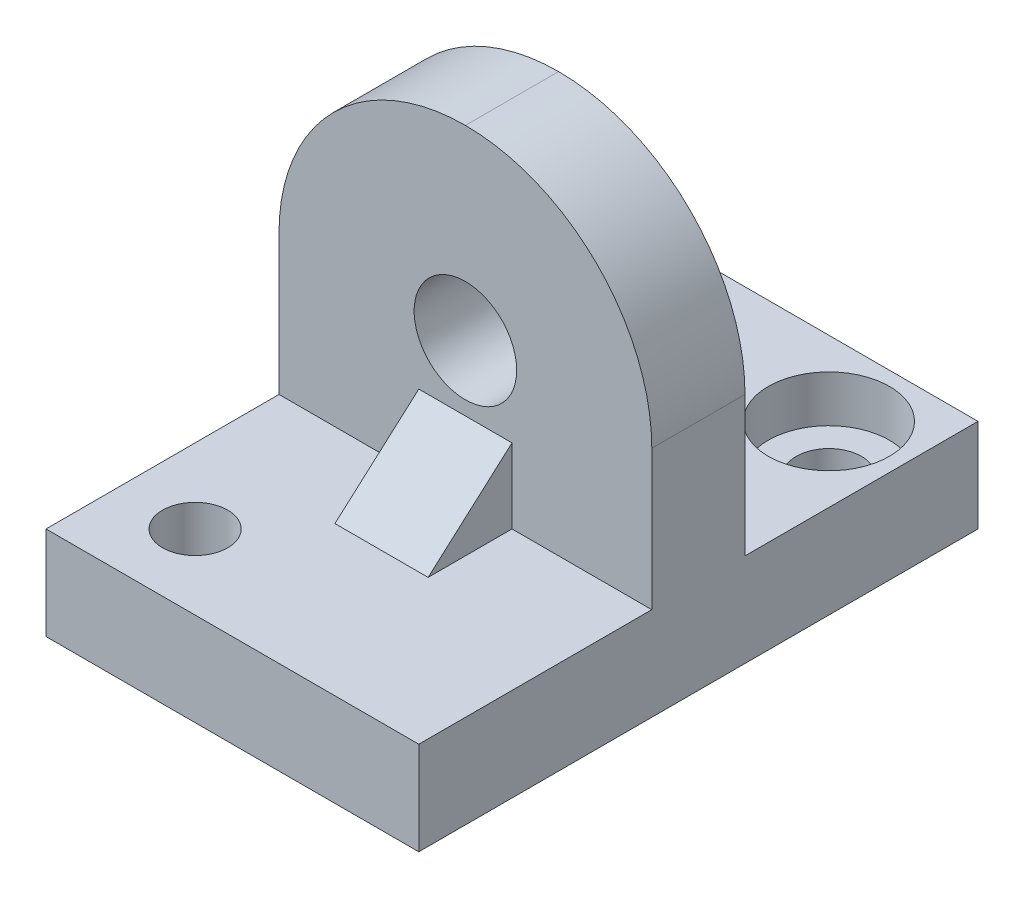
SolidWorks part; units mm, degrees
ref_plane "Спереди" through (0, 0, 0) normal (0, 0, 1) x (1, 0, 0)
ref_plane "Сверху" through (0, 0, 0) normal (0, 1, 0) x (1, 0, 0)
ref_plane "Справа" through (0, 0, 0) normal (1, 0, 0) x (0, 0, -1)
sketch "Эскиз1" plane through (0, 0, 0) normal (1, 0, 0) x (0, 0, -1)
  line L0 (-14, -17.5) -> (-5, -9.5)
  line L1 (-5, -17.5) -> (5, -17.5)
  line L2 (-5, -17.5) -> (-5, 17.5)
  line L3 (-5, 17.5) -> (5, 17.5)
  line L4 (5, -17.5) -> (5, 17.5)
  line L5 (-5, -17.5) -> (5, 17.5) construction
  line L6 (-5, 17.5) -> (5, -17.5) construction
  line L7 (-30, -27.5) -> (30, -27.5)
  line L8 (-30, -27.5) -> (-30, -17.5)
  line L9 (-30, -17.5) -> (30, -17.5)
  line L10 (30, -27.5) -> (30, -17.5)
  line L11 (-30, -27.5) -> (30, -17.5) construction
  line L12 (-30, -17.5) -> (30, -27.5) construction
  line L13 (5, -9.5) -> (14, -17.5)
  point P0 (0, 0)
  point P6 (0, -22.5)
  dimension "D1" = 60
  dimension "D2" = 10
  dimension "D3" = 45
  dimension "D4" = 9
  dimension "D5" = 9
  dimension "D6" = 8
extrude "Бобышка-Вытянуть1" add sketch "Эскиз1" along normal blind 20 and the other way blind 20 contours L1 L4 L3 L2 | L7 L10 L9 L1 L8 region at (0, -22.5, 0) region at (0, 0, 0)
fillet "Скругление1" radius 20 2 edges at (-20, 17.5, 0) (20, 17.5, 0)
sketch "Эскиз2" plane through (0, 0, 5) normal (0, 0, 1) x (1, 0, 0)
  circle A0 centre (0, -2.5) radius 5.5
  dimension "D1" = 11
extrude "Вырез-Вытянуть1" cut sketch "Эскиз2" against normal through all
extrude "Бобышка-Вытянуть2" add sketch "Эскиз1<3>" along normal blind 5 and the other way blind 5 contours L0 L9 L2 | L13 L4 L9 region at (0, -14.8333, 8) region at (0, -14.8333, -8)
sketch "Эскиз1<3>" plane through (0, 0, 0) normal (1, 0, 0) x (0, 0, -1) same geometry as "Эскиз1"
sketch "Эскиз3" plane through (0, -17.5, 0) normal (0, 1, 0) x (1, 0, 0)
  line L0 (-20, -30) -> (20, -30) construction
  line L1 (-20, -30) -> (-20, -5) construction
  line L2 (20, 5) -> (20, 30) construction
  line L3 (-20, 30) -> (20, 30) construction
  circle A0 centre (-12, -22) radius 3.5
  circle A1 centre (12, 22) radius 3.5
  dimension "D5" = 7
  dimension "D1" = 8
  dimension "D2" = 8
  dimension "D3" = 8
  dimension "D4" = 8
extrude "Вырез-Вытянуть2" cut sketch "Эскиз3" against normal through all
sketch "Эскиз4" plane through (0, -17.5, 0) normal (0, 1, 0) x (1, 0, 0)
  circle A0 centre (12, 22) radius 6.5
  dimension "D1" = 13
extrude "Вырез-Вытянуть3" cut sketch "Эскиз4" against normal blind 5
